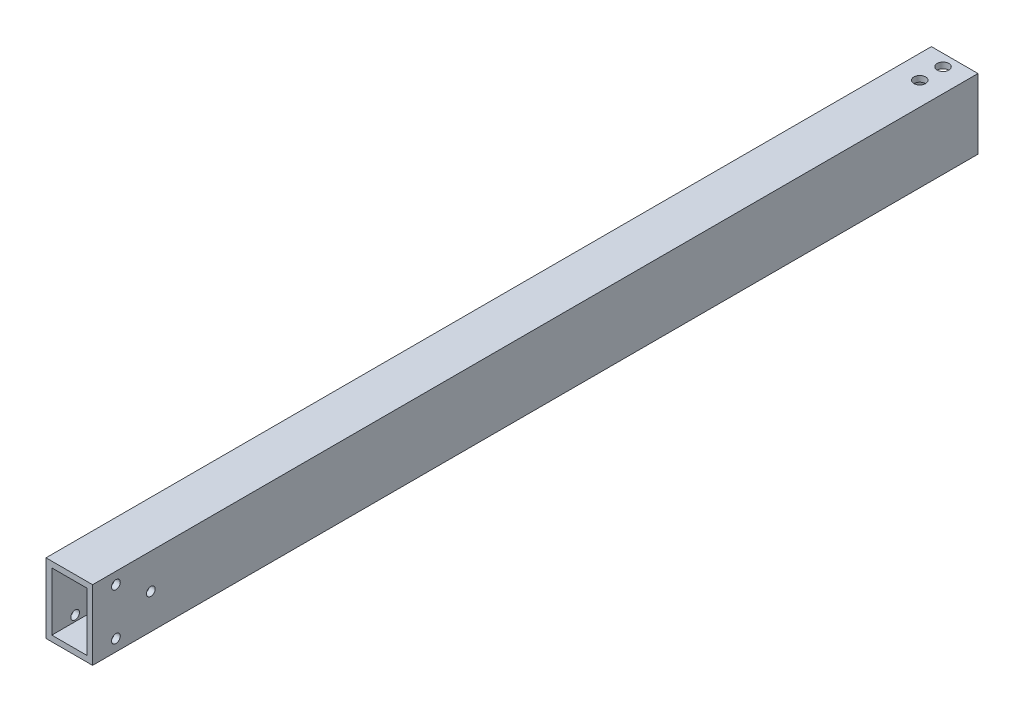
SolidWorks part; units mm, degrees
material "6061-T6 (SS)"
ref_plane "Front Plane" through (0, 0, 0) normal (0, 0, 1) x (1, 0, 0)
ref_plane "Top Plane" through (0, 0, 0) normal (0, 1, 0) x (1, 0, 0)
ref_plane "Right Plane" through (0, 0, 0) normal (1, 0, 0) x (0, 0, -1)
sketch "Sketch1" plane through (0, 0, 0) normal (0, 0, 1) x (1, 0, 0)
  line L1 (-12.7, 19.05) -> (12.7, 19.05)
  line L2 (-12.7, 19.05) -> (-12.7, -19.05)
  line L3 (-12.7, -19.05) -> (12.7, -19.05)
  line L4 (12.7, 19.05) -> (12.7, -19.05)
  line L5 (-12.7, 19.05) -> (12.7, -19.05) construction
  line L6 (-12.7, -19.05) -> (12.7, 19.05) construction
  line L7 (-9.525, -15.875) -> (9.525, -15.875)
  line L8 (-9.525, -15.875) -> (-9.525, 15.875)
  line L9 (-9.525, 15.875) -> (9.525, 15.875)
  line L10 (9.525, -15.875) -> (9.525, 15.875)
  line L11 (-9.525, -15.875) -> (9.525, 15.875) construction
  line L12 (-9.525, 15.875) -> (9.525, -15.875) construction
  point P0 (0, 0)
  point P6 (0, 0)
  dimension "D1" = 25.4
  dimension "D2" = 38.1
  dimension "D3" = 3.175
  dimension "D4" = 3.175
extrude "Boss-Extrude1" add sketch "Sketch1" along normal blind 482.6
sketch "Sketch2" plane through (0, 19.05, 0) normal (0, 1, 0) x (1, 0, 0)
  line L2 (-12.7, 0) -> (12.7, 0) construction
  circle A0 centre (0, -19.05) radius 3.175
  circle A1 centre (0, -6.35) radius 3.175
  dimension "D1" = 6.35
  dimension "D2" = 6.35
  dimension "D3" = 6.35
  dimension "D4" = 12.7
extrude "Cut-Extrude1" cut sketch "Sketch2" against normal through all
sketch "Sketch3" plane through (-12.7, 0, 0) normal (-1, 0, 0) x (0, 0, 1)
  line L0 (482.6, 19.05) -> (482.6, -19.05) construction
  line L1 (482.6, 19.05) -> (0, 19.05) construction
  circle A0 centre (469.9, -12.7) radius 2.3813
  circle A1 centre (469.9, 12.7) radius 2.3813
  dimension "D1" = 4.7625
  dimension "D2" = 4.7625
  dimension "D3" = 12.7
  dimension "D4" = 12.7
  dimension "D5" = 25.4
  dimension "D6" = 6.35
extrude "Cut-Extrude2" cut sketch "Sketch3" against normal through all
sketch "Sketch4" plane through (-12.7, 0, 0) normal (-1, 0, 0) x (0, 0, 1)
  line L0 (482.6, 19.05) -> (482.6, -19.05) construction
  line L1 (482.6, 19.05) -> (0, 19.05) construction
  circle A0 centre (450.85, 0) radius 2.3813
  dimension "D1" = 4.7625
  dimension "D2" = 31.75
  dimension "D3" = 19.05
extrude "Cut-Extrude3" cut sketch "Sketch4" against normal through all
